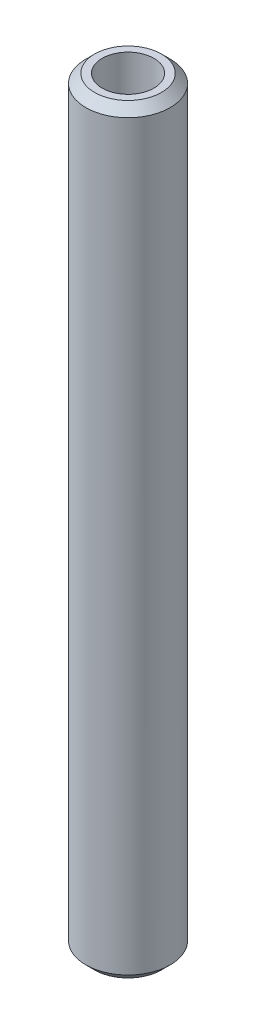
SolidWorks part; units mm, degrees
ref_plane "Front Plane" through (0, 0, 0) normal (0, 0, 1) x (1, 0, 0)
ref_plane "Top Plane" through (0, 0, 0) normal (0, 1, 0) x (1, 0, 0)
ref_plane "Right Plane" through (0, 0, 0) normal (1, 0, 0) x (0, 0, -1)
sketch "Sketch1" plane through (0, 0, 0) normal (0, 1, 0) x (1, 0, 0)
  circle A0 centre (0, 0) radius 27.5
  dimension "SHAFT_OD" = 55
extrude "Boss-Extrude1" add sketch "Sketch1" along normal blind 495.9909
sketch "Sketch2" plane through (0, 0, 0) normal (0, 1, 0) x (1, 0, 0)
  circle A0 centre (0, 0) radius 16.8894
  dimension "BORE_D" = 33.7788
extrude "Cut-Extrude1" cut sketch "Sketch2" along normal through all
chamfer "Chamfer1" distance 5.7122 angle 45 2 edges at (0, 495.9909, 27.5) (0, 0, 27.5)
